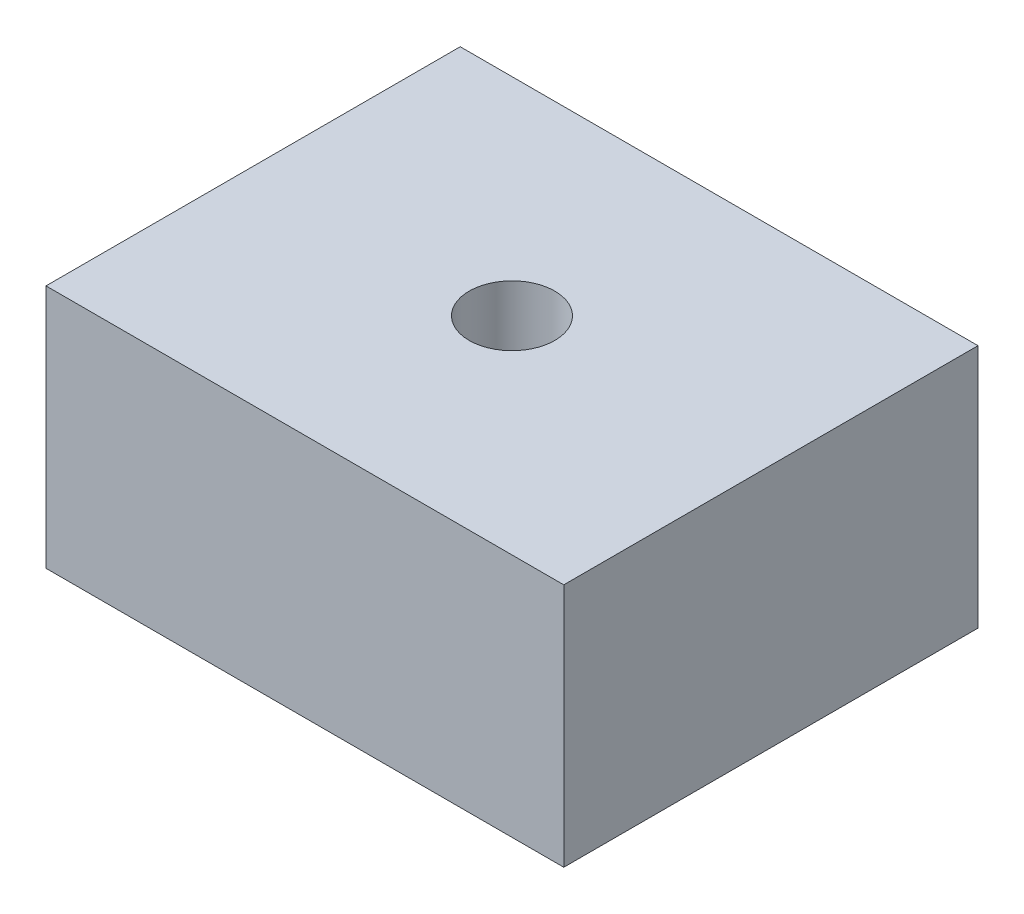
SolidWorks part; units mm, degrees
ref_plane "Front Plane" through (0, 0, 0) normal (0, 0, 1) x (1, 0, 0)
ref_plane "Top Plane" through (0, 0, 0) normal (0, 1, 0) x (1, 0, 0)
ref_plane "Right Plane" through (0, 0, 0) normal (1, 0, 0) x (0, 0, -1)
sketch "Sketch1" plane through (0, 0, 0) normal (0, 1, 0) x (1, 0, 0)
  line L1 (-31.75, 25.4) -> (31.75, 25.4)
  line L2 (-31.75, 25.4) -> (-31.75, -25.4)
  line L3 (-31.75, -25.4) -> (31.75, -25.4)
  line L4 (31.75, 25.4) -> (31.75, -25.4)
  line L5 (-31.75, 25.4) -> (31.75, -25.4) construction
  line L6 (-31.75, -25.4) -> (31.75, 25.4) construction
  circle A0 centre (0, 0) radius 5.25
  dimension "D1" = 50.8
  dimension "D2" = 63.5
extrude "Boss-Extrude1" add sketch "Sketch1" along normal blind 30
